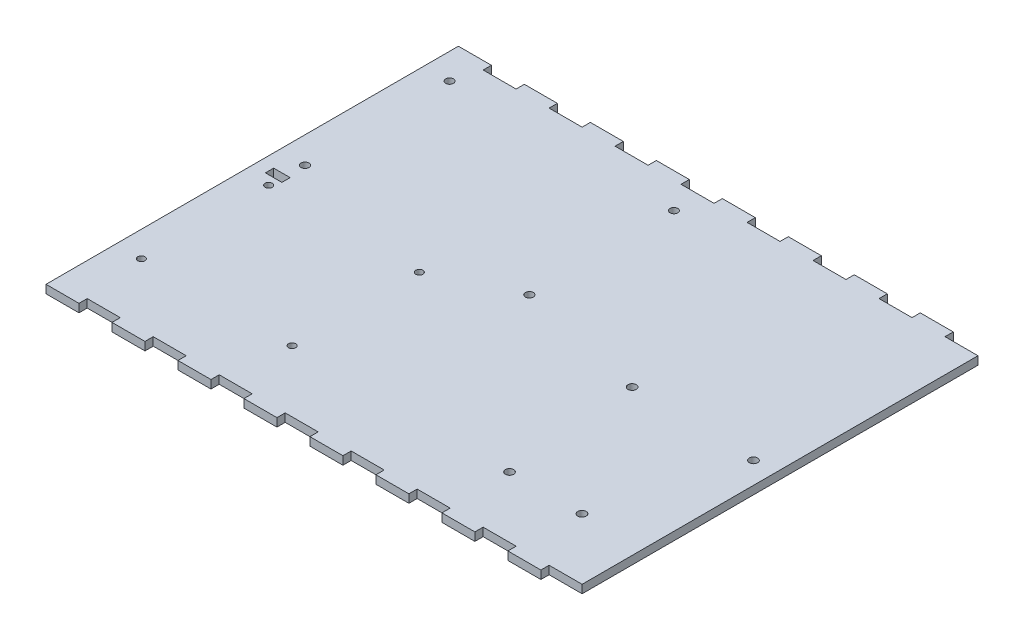
SolidWorks part; units mm, degrees
ref_plane "Front" through (0, 0, 0) normal (0, 0, 1) x (1, 0, 0)
ref_plane "Top" through (0, 0, 0) normal (0, 1, 0) x (1, 0, 0)
ref_plane "Right" through (0, 0, 0) normal (1, 0, 0) x (0, 0, -1)
sketch "Sketch1" plane through (0, 0, 0) normal (0, 1, 0) x (1, 0, 0)
  line L1 (0, 0) -> (203.2, 0)
  line L2 (0, 0) -> (0, 152.4)
  line L3 (0, 152.4) -> (203.2, 152.4)
  line L4 (203.2, 0) -> (203.2, 152.4)
  dimension "D1" = 203.2
  dimension "D2" = 152.4
extrude "Boss-Extrude1" add sketch "Sketch1" along normal blind 3.175
sketch "Sketch2" plane through (0, 3.175, 0) normal (0, 1, 0) x (1, 0, 0)
  line L0 (25.4, 0) -> (25.4, -3.175)
  line L1 (0, 0) -> (12.7, 0)
  line L2 (0, 0) -> (0, -3.175)
  line L3 (0, -3.175) -> (12.7, -3.175)
  line L4 (12.7, 0) -> (12.7, -3.175)
  line L5 (25.4, 0) -> (38.1, 0)
  line L6 (38.1, 0) -> (38.1, -3.175)
  line L7 (25.4, -3.175) -> (38.1, -3.175)
  line L8 (50.8, 0) -> (50.8, -3.175)
  line L9 (50.8, 0) -> (63.5, 0)
  line L10 (63.5, 0) -> (63.5, -3.175)
  line L11 (50.8, -3.175) -> (63.5, -3.175)
  line L12 (76.2, 0) -> (76.2, -3.175)
  line L13 (76.2, 0) -> (88.9, 0)
  line L14 (88.9, 0) -> (88.9, -3.175)
  line L15 (76.2, -3.175) -> (88.9, -3.175)
  line L16 (101.6, 0) -> (101.6, -3.175)
  line L17 (101.6, 0) -> (114.3, 0)
  line L18 (114.3, 0) -> (114.3, -3.175)
  line L19 (101.6, -3.175) -> (114.3, -3.175)
  line L20 (127, 0) -> (127, -3.175)
  line L21 (127, 0) -> (139.7, 0)
  line L22 (139.7, 0) -> (139.7, -3.175)
  line L23 (127, -3.175) -> (139.7, -3.175)
  line L24 (152.4, 0) -> (152.4, -3.175)
  line L25 (152.4, 0) -> (165.1, 0)
  line L26 (165.1, 0) -> (165.1, -3.175)
  line L27 (152.4, -3.175) -> (165.1, -3.175)
  line L28 (177.8, 0) -> (177.8, -3.175)
  line L29 (177.8, 0) -> (190.5, 0)
  line L30 (190.5, 0) -> (190.5, -3.175)
  line L31 (177.8, -3.175) -> (190.5, -3.175)
  line L32 (0, 76.2) -> (203.2, 76.2) construction
  line L33 (0, 152.4) -> (0, 0) construction
  line L34 (203.2, 0) -> (203.2, 152.4) construction
  line L35 (177.8, 152.4) -> (190.5, 152.4)
  line L36 (190.5, 152.4) -> (190.5, 155.575)
  line L37 (177.8, 155.575) -> (190.5, 155.575)
  line L38 (177.8, 152.4) -> (177.8, 155.575)
  line L39 (152.4, 152.4) -> (165.1, 152.4)
  line L40 (165.1, 152.4) -> (165.1, 155.575)
  line L41 (152.4, 155.575) -> (165.1, 155.575)
  line L42 (152.4, 152.4) -> (152.4, 155.575)
  line L43 (127, 152.4) -> (139.7, 152.4)
  line L44 (139.7, 152.4) -> (139.7, 155.575)
  line L45 (127, 155.575) -> (139.7, 155.575)
  line L46 (127, 152.4) -> (127, 155.575)
  line L47 (101.6, 152.4) -> (114.3, 152.4)
  line L48 (114.3, 152.4) -> (114.3, 155.575)
  line L49 (101.6, 155.575) -> (114.3, 155.575)
  line L50 (101.6, 152.4) -> (101.6, 155.575)
  line L51 (76.2, 152.4) -> (88.9, 152.4)
  line L52 (88.9, 152.4) -> (88.9, 155.575)
  line L53 (76.2, 155.575) -> (88.9, 155.575)
  line L54 (76.2, 152.4) -> (76.2, 155.575)
  line L55 (50.8, 152.4) -> (63.5, 152.4)
  line L56 (63.5, 152.4) -> (63.5, 155.575)
  line L57 (50.8, 155.575) -> (63.5, 155.575)
  line L58 (50.8, 152.4) -> (50.8, 155.575)
  line L59 (25.4, 152.4) -> (38.1, 152.4)
  line L60 (38.1, 152.4) -> (38.1, 155.575)
  line L61 (25.4, 155.575) -> (38.1, 155.575)
  line L62 (25.4, 152.4) -> (25.4, 155.575)
  line L63 (0, 155.575) -> (12.7, 155.575)
  line L64 (12.7, 152.4) -> (12.7, 155.575)
  line L65 (0, 152.4) -> (12.7, 152.4)
  line L66 (0, 152.4) -> (0, 155.575)
  dimension "D1" = 3.175
  dimension "D2" = 12.7
  dimension "D3" = 8
extrude "Boss-Extrude2" add sketch "Sketch2" against normal blind 3.175 separate body
sketch "Sketch4" plane through (-65.6185, 3.175, -114.5289) normal (0, 1, 0) x (1, 0, 0)
  line L0 (104.4685, -38.3289) -> (104.4685, -94.3289) construction
  line L1 (74.9685, -94.3289) -> (153.9685, -94.3289) construction
  line L2 (71.9685, -91.3289) -> (71.9685, -41.3289) construction
  line L3 (74.9685, -38.3289) -> (153.9685, -38.3289) construction
  line L4 (156.9685, -91.3289) -> (156.9685, -41.3289) construction
  line L10 (65.6185, 37.8711) -> (65.6185, -114.5289) construction
  line L12 (268.8185, 37.8711) -> (65.6185, 37.8711) construction
  arc A0 (74.9685, -94.3289) -> (71.9685, -91.3289) centre (74.9685, -91.3289) cw construction
  arc A1 (153.9685, -94.3289) -> (156.9685, -91.3289) centre (153.9685, -91.3289) ccw construction
  arc A2 (153.9685, -38.3289) -> (156.9685, -41.3289) centre (153.9685, -41.3289) cw construction
  arc A3 (71.9685, -41.3289) -> (74.9685, -38.3289) centre (74.9685, -41.3289) cw construction
  circle A4 centre (75.4685, -41.8289) radius 1.375
  circle A5 centre (75.4685, -90.8289) radius 1.375
  circle A6 centre (133.4685, -90.8289) radius 1.375
  circle A7 centre (133.4685, -41.8289) radius 1.375
  point P7 (71.9685, -94.3289)
  point P12 (156.9685, -38.3289)
  point P15 (71.9685, -38.3289)
  dimension "D3" = 3
  dimension "D4" = 2.75
  dimension "D1" = 56
  dimension "D2" = 85
  dimension "D5" = 49
  dimension "D6" = 3.5
  dimension "D7" = 3.5
  dimension "D8" = 58
  dimension "D9" = 6.35
  dimension "D10" = 76.2
extrude "Cut-Extrude1" cut sketch "Sketch4" against normal through all
sketch "Sketch5" plane through (-58.3327, 3.175, -175.8659) normal (0, 1, 0) x (0, 0, 1)
  line L0 (86.4754, 202.6489) -> (86.4754, 255.9489) construction
  line L1 (86.4754, 255.9489) -> (150.2443, 255.9489) construction
  line L2 (150.2443, 255.9489) -> (152.3754, 253.8178) construction
  line L3 (155.2754, 240.1078) -> (155.2754, 208.2989) construction
  line L4 (155.2754, 208.2989) -> (152.3754, 205.3989) construction
  line L5 (152.3754, 205.3989) -> (152.3754, 202.6489) construction
  line L6 (152.3754, 202.6489) -> (86.4754, 202.6489) construction
  line L7 (152.3754, 253.8178) -> (152.3754, 243.0078) construction
  line L8 (152.3754, 243.0078) -> (155.2754, 240.1078) construction
  circle A0 centre (100.4754, 205.3989) radius 1.6
  circle A1 centre (101.5754, 253.1989) radius 1.6
  circle A2 centre (152.3754, 210.0989) radius 1.6
  circle A3 centre (152.3754, 237.9989) radius 1.6
  dimension "D3" = 3.2
  dimension "D12" = 50.8
  dimension "D7" = 51.9
  dimension "D1" = 53.3
  dimension "D2" = 68.8
  dimension "D4" = 15.2
  dimension "D5" = 14
  dimension "D6" = 2.75
  dimension "D8" = 51.9
  dimension "D9" = 1.1
  dimension "D10" = 4.7
  dimension "D11" = 2.75
  dimension "D13" = 45
  dimension "D14" = 45
  dimension "D16" = 45
extrude "Cut-Extrude2" cut sketch "Sketch5" against normal through all
sketch "Sketch10" plane through (154.7382, 3.175, -89.7842) normal (0, 1, 0) x (0, 0, -1)
  line L0 (-4.9142, 54.3882) -> (53.9458, 54.3882) construction
  line L1 (-7.2342, 56.7082) -> (-7.2342, 146.0682) construction
  line L2 (-4.9142, 148.3882) -> (53.9458, 148.3882) construction
  line L3 (56.2658, 56.7082) -> (56.2658, 146.0682) construction
  line L4 (-7.2342, 54.3882) -> (56.2658, 148.3882) construction
  line L5 (-7.2342, 148.3882) -> (56.2658, 54.3882) construction
  line L6 (62.6158, 154.7382) -> (-89.7842, 154.7382) construction
  line L7 (62.6158, -48.4618) -> (62.6158, 154.7382) construction
  line L8 (-3.4238, 144.5682) -> (-3.4238, 58.2082) construction
  arc A0 (-4.9142, 54.3882) -> (-7.2342, 56.7082) centre (-4.9142, 56.7082) cw construction
  arc A1 (53.9458, 54.3882) -> (56.2658, 56.7082) centre (53.9458, 56.7082) ccw construction
  arc A2 (53.9458, 148.3882) -> (56.2658, 146.0682) centre (53.9458, 146.0682) cw construction
  arc A3 (-4.9142, 148.3882) -> (-7.2342, 146.0682) centre (-4.9142, 146.0682) ccw construction
  circle A4 centre (-66.0842, 86.8882) radius 1.375 construction
  circle A5 centre (-3.4238, 144.5682) radius 1.535
  circle A6 centre (52.4558, 144.7859) radius 1.5
  circle A7 centre (-3.4238, 58.2082) radius 1.535
  circle A8 centre (52.4558, 58.4259) radius 1.5
  point P0 (24.5158, 101.3882)
  dimension "D3" = 2.32
  dimension "D6" = 3.07
  dimension "D7" = 3
  dimension "D1" = 63.5
  dimension "D2" = 94
  dimension "D4" = 6.35
  dimension "D5" = 6.35
  dimension "D8" = 55.88
  dimension "D9" = 27.94
  dimension "D10" = 43.18
  dimension "D12" = 86.36
  dimension "D11" = 2
extrude "Cut-Extrude3" cut sketch "Sketch10" against normal through all both and the other way through all
combine bodies "Combine1" operation type add bodies to combine 102 104 106 108 110 112 114 116 117 122 103 105 107 109 111 113 115
sketch "Sketch11" plane through (0, 3.175, 0) normal (0, 1, 0) x (1, 0, 0)
  line L0 (0, 76.2) -> (203.2, 76.2) construction
  line L1 (0, 155.575) -> (0, -3.175) construction
  line L2 (203.2, 0) -> (203.2, 152.4) construction
  line L4 (5.08, 76.2) -> (11.43, 76.2)
  line L5 (5.08, 76.2) -> (5.08, 79.375)
  line L6 (5.08, 79.375) -> (11.43, 79.375)
  line L7 (11.43, 76.2) -> (11.43, 79.375)
  dimension "D1" = 3.175
  dimension "D2" = 6.35
  dimension "D3" = 5.08
extrude "Cut-Extrude4" cut sketch "Sketch11" against normal through all
